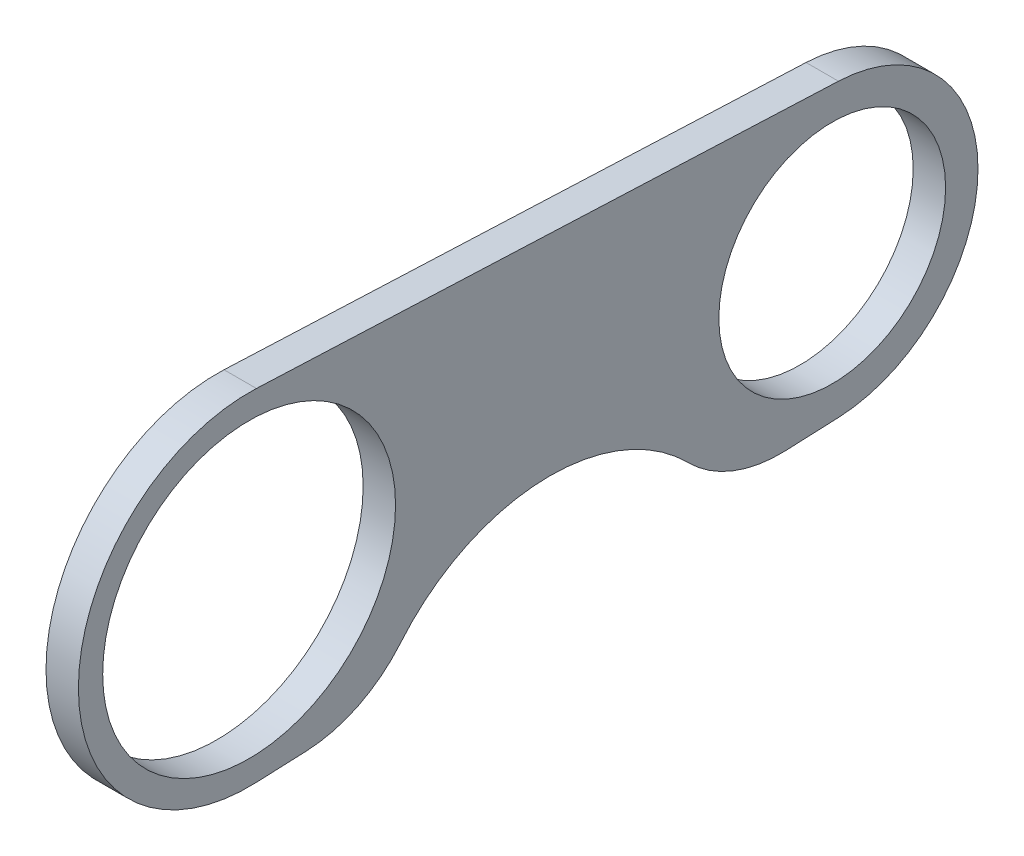
SolidWorks part; units mm, degrees
material "6061-T6 (SS)"
ref_plane "Front" through (0, 0, 0) normal (0, 0, 1) x (1, 0, 0)
ref_plane "Top" through (0, 0, 0) normal (0, 1, 0) x (1, 0, 0)
ref_plane "Right" through (0, 0, 0) normal (1, 0, 0) x (0, 0, -1)
sketch "Sketch1" plane through (0, 0, 0) normal (1, 0, 0) x (0, 0, -1)
  line L0 (-27.8592, 16.7169) -> (29.1862, 14.2744)
  line L3 (-27.8592, -16.7169) -> (29.1862, -14.2744)
  line L4 (-28.575, 0) -> (28.575, 0) construction
  circle A2 centre (-28.575, 0) radius 14.351
  circle A3 centre (28.575, 0) radius 11.1125
  arc A4 (29.1862, -14.2744) -> (29.1862, 14.2744) centre (28.575, 0) ccw
  arc A5 (-27.8592, 16.7169) -> (-27.8592, -16.7169) centre (-28.575, 0) ccw
  point P13 (0, 0)
  dimension "D1" = 28.702
  dimension "D2" = 2.3812
  dimension "D4" = 22.225
  dimension "D3" = 3.175
  dimension "D5" = 57.15
extrude "Boss-Extrude1" add sketch "Sketch1" along normal blind 3.175
sketch "Sketch2" plane through (3.175, 0, 0) normal (1, 0, 0) x (0, 0, -1)
  circle A0 centre (0.9098, -24.13) radius 19.05
  circle A1 centre (-28.575, 0) radius 14.351 construction
  dimension "D1" = 38.1
  dimension "D2" = 38.1
  dimension "D3" = 24.13
extrude "Cut-Extrude1" cut sketch "Sketch2" against normal through all
fillet "Fillet1" radius 12.7 2 edges at (1.5875, -14.7746, -17.5043) (1.5875, -16.2273, 16.4237)
